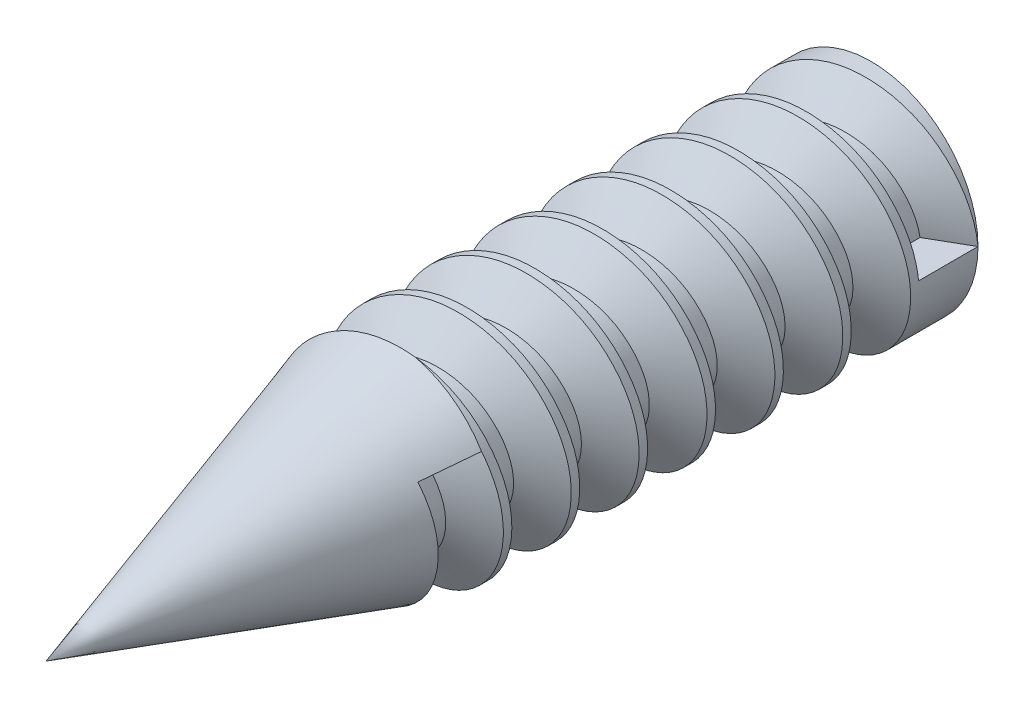
SolidWorks part; units mm, degrees
ref_plane "前视基准面" through (0, 0, 0) normal (0, 0, 1) x (1, 0, 0)
ref_plane "上视基准面" through (0, 0, 0) normal (0, 1, 0) x (1, 0, 0)
ref_plane "右视基准面" through (0, 0, 0) normal (1, 0, 0) x (0, 0, -1)
sketch "草图1" plane through (0, 0, 0) normal (0, 0, 1) x (1, 0, 0)
  circle A0 centre (0, 0) radius 2
extrude "凸台-拉伸1" add sketch "草图1" along normal blind 9 contours A0
sketch "草图2" plane through (0, 0, 0) normal (1, 0, 0) x (0, 0, -1)
  line L0 (-9, 0) -> (-15.4377, 0)
  line L1 (-9, 2) -> (-9, -2) construction
  line L2 (-15.4377, 0) -> (-9, 2)
  line L3 (-9, 2) -> (-9, 0)
  point P5 (-14.8672, 0)
  point P8 (-15.4377, 0)
revolve "旋转1" add sketch "草图2" angle 360 about L0
thread "螺纹线1" pitch 1.27 method cut profile "螺纹线轮廓1" start angle 0, offset 0, length 0, pitch 1.27, diameter 4
ref_plane "基准面1" through (2, 0, 0) normal (0, -1, 0) x (1, 0, 0)
sketch "螺纹线轮廓1" plane through (2, 0, 0) normal (0, -1, 0) x (1, 0, 0)
  line L0 (0, 0) -> (0, 1.27) construction
  line L11 (0, 0) -> (0, 1.1112)
  line L12 (0, 1.1112) -> (-0.6874, 0.7144)
  line L13 (-0.6874, 0.7144) -> (-0.6874, 0.3969)
  line L15 (-0.6874, 0.3969) -> (0, 0)
  line L17 (-0.6874, 0.5556) -> (0, 0.5556) construction
  point P2 (0, 0)
  dimension "Pitch" = 1.27
  dimension "Profile_Angle" = 60
  dimension "Profile_Land" = 0.3175
  dimension "Profile_Height" = 0.6874
